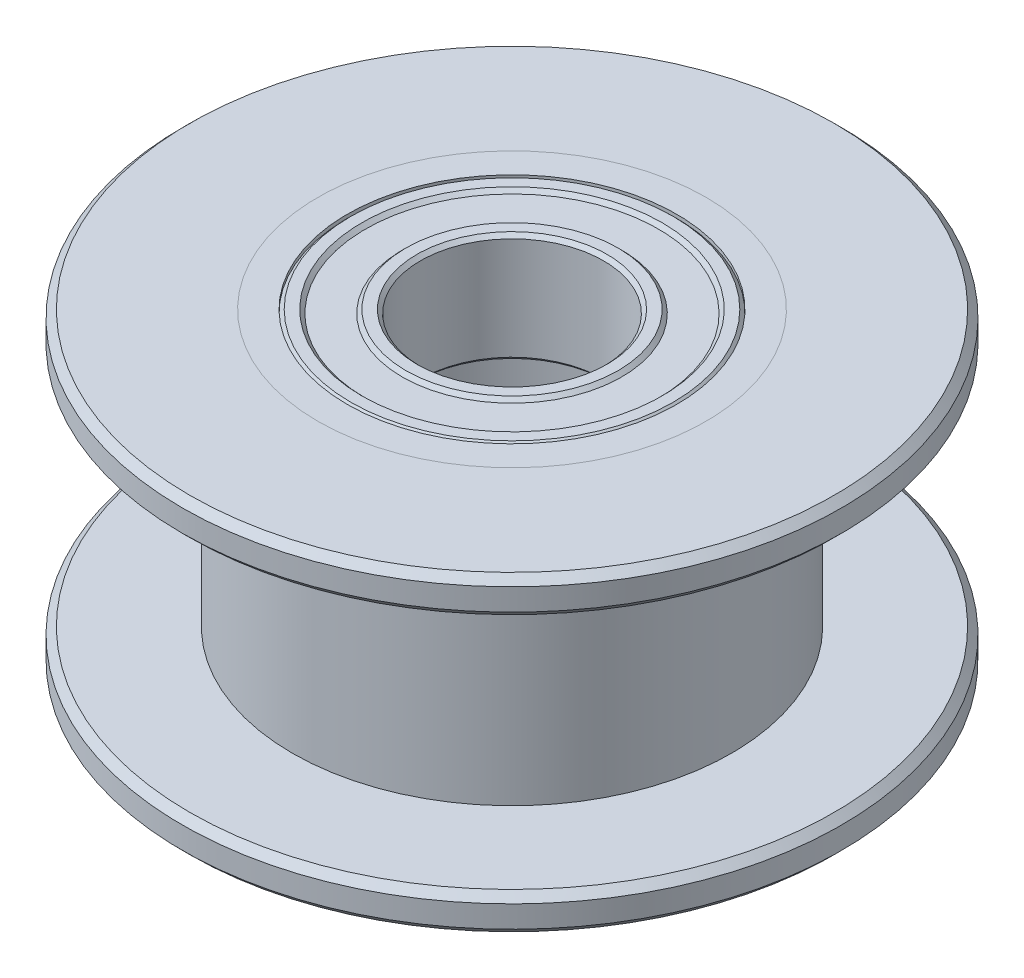
SolidWorks part; units mm, degrees
ref_plane "Přední rovina" through (0, 0, 0) normal (0, 0, 1) x (1, 0, 0)
ref_plane "Horní rovina" through (0, 0, 0) normal (0, 1, 0) x (1, 0, 0)
ref_plane "Pravá rovina" through (0, 0, 0) normal (1, 0, 0) x (0, 0, -1)
sketch "Skica1" plane through (0, 0, 0) normal (0, 0, 1) x (1, 0, 0)
  line L0 (0, 8.5) -> (0, 0) construction
  line L1 (-4.5, 8.5) -> (-5.3, 8.5)
  line L2 (-5.3, 8.5) -> (-5.3, 7.5)
  line L3 (-5.3, 7.5) -> (-6, 7.5)
  line L4 (-6, 7.5) -> (-6, 1)
  line L5 (-6, 1) -> (-5.3, 1)
  line L6 (-5.3, 1) -> (-5.3, 0)
  line L7 (-5.3, 0) -> (-4.5, 0)
  line L8 (-4.5, 0) -> (-4.5, 3)
  line L9 (-4.5, 3) -> (-4, 3)
  line L10 (-4, 3) -> (-4, 5.5)
  line L11 (-4, 5.5) -> (-4.5, 5.5)
  line L12 (-4.5, 5.5) -> (-4.5, 8.5)
  dimension "D1" = 6
  dimension "D2" = 0.8
  dimension "D3" = 0.7
  dimension "D4" = 0.5
  dimension "D5" = 2.5
  dimension "D6" = 3
  dimension "D7" = 3
  dimension "D8" = 8.5
  dimension "D9" = 1
  dimension "D10" = 1
  dimension "D11" = 6.5
revolve "Rotovat1" add sketch "Skica1" angle 360 about L0
sketch "Skica2" plane through (0, 7.5, 0) normal (0, 1, 0) x (1, 0, 0)
  circle A0 centre (0, 0) radius 5.3
  circle A2 centre (0, 0) radius 9
  dimension "D1" = 10.6
  dimension "D3" = 18
extrude "Přidat vysunutím1" add sketch "Skica2" along normal blind 1 separate body
chamfer "Zkosení1" distance 0.2 angle 45 2 edges at (0, 7.5, 9) (0, 8.5, 9)
sketch "Skica3" plane through (0, 1, 0) normal (0, -1, 0) x (1, 0, 0)
  circle A0 centre (0, 0) radius 5.3
  circle A2 centre (0, 0) radius 9
  dimension "D1" = 10.6
  dimension "D3" = 18
extrude "Přidat vysunutím2" add sketch "Skica3" along normal blind 1 separate body
chamfer "Zkosení2" distance 0.2 angle 45 2 edges at (0, 0, -9) (0, 1, -9)
sketch "Skica4" plane through (0, 5.5, 0) normal (0, 1, 0) x (1, 0, 0)
  circle A0 centre (0, 0) radius 2.5
  circle A1 centre (0, 0) radius 3
  circle A2 centre (0, 0) radius 4
  circle A3 centre (0, 0) radius 4.5
  circle M1 centre (0, 0) radius 4.5
  circle M2 centre (0, 0) radius 4
extrude "Přidat vysunutím3" add sketch "Skica4" along normal blind 3 separate body contours M1 M2 | A1 A0 region at (-2.9151, 5.5, 0) region at (-4.3727, 5.5, 0)
extrude "Přidat vysunutím4" add sketch "Skica4<4>" along normal blind 2.8 from offset 0.1 separate body contours A1 M2 region at (-3.8869, 5.5, 0)
sketch "Skica4<4>" plane through (0, 5.5, 0) normal (0, 1, 0) x (1, 0, 0) same geometry as "Skica4"
chamfer "Zkosení3" distance 0.1 angle 45 4 edges at (0, 8.5, 3) (0, 8.5, 2.5) (0, 5.5, 3) (0, 5.5, 2.5)
chamfer "Zkosení4" distance 0.1 angle 45 4 edges at (0, 8.5, 4.5) (0, 8.5, 4) (0, 5.5, 4.5) (0, 5.5, 4)
sketch "Skica5" plane through (0, 3, 0) normal (0, -1, 0) x (1, 0, 0)
  circle A0 centre (0, 0) radius 2.5
  circle A1 centre (0, 0) radius 3
  circle A2 centre (0, 0) radius 4
  circle A3 centre (0, 0) radius 4.5
  circle M1 centre (0, 0) radius 4
  circle M2 centre (0, 0) radius 4.5
extrude "Přidat vysunutím6" add sketch "Skica5" along normal blind 3 separate body contours A1 A0 | M2 M1 region at (-2.9151, 3, 0) region at (-4.3727, 3, 0)
chamfer "Zkosení5" distance 0.1 angle 45 4 edges at (0, 0, -3) (0, 0, -2.5) (0, 3, -3) (0, 3, -2.5)
chamfer "Zkosení6" distance 0.1 angle 45 4 edges at (0, 3, -4.5) (0, 0, -4.5) (0, 0, -4) (0, 3, -4)
extrude "Přidat vysunutím7" add sketch "Skica5<4>" along normal blind 2.8 from offset 0.1 separate body contours A1 M1 region at (-3.8869, 3, 0)
sketch "Skica5<4>" plane through (0, 3, 0) normal (0, -1, 0) x (1, 0, 0) same geometry as "Skica5"
